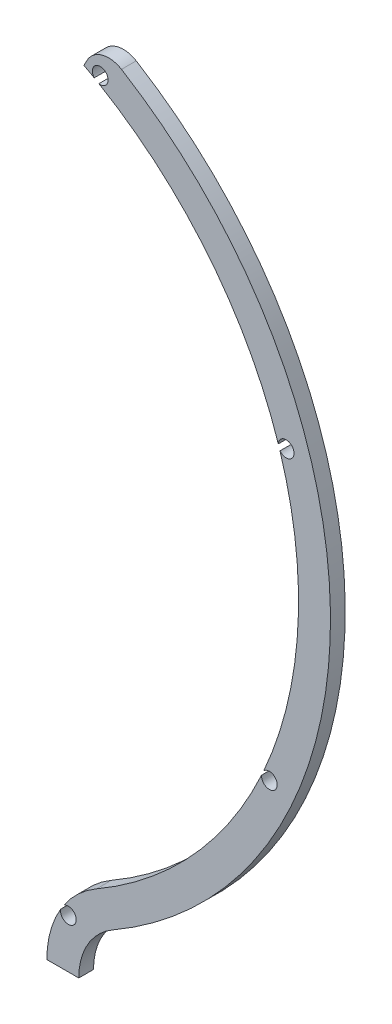
SolidWorks part; units mm, degrees
material "Thornel Mat VMA"
ref_plane "Front Plane" through (0, 0, 0) normal (0, 0, 1) x (1, 0, 0)
ref_plane "Top Plane" through (0, 0, 0) normal (0, 1, 0) x (1, 0, 0)
ref_plane "Right Plane" through (0, 0, 0) normal (1, 0, 0) x (0, 0, -1)
sketch "Sketch1" plane through (0, 0, 0) normal (0, 0, 1) x (1, 0, 0)
  line L0 (23.5, 0) -> (35.5, 0) construction
  line L1 (31, 0) -> (37.5, 0)
  line L3 (39.1768, 162.602) -> (38.5438, 161.4089)
  circle A0 centre (41.8718, 161.2805) radius 1.6
  circle A1 centre (79.7216, 114.3972) radius 1.6
  circle A2 centre (76.2992, 54.2395) radius 1.6
  circle A3 centre (35.3905, 10) radius 1.6
  arc A4 (38.5438, 161.4089) -> (41.1218, 17.5314) centre (0, 88.7564) cw
  arc A5 (41.1218, 17.5314) -> (31, 0) centre (51.2436, 0) ccw
  arc A6 (43.3718, 13.6343) -> (35.5, 0) centre (51.2436, 0) ccw construction
  arc A7 (43.3718, 13.6343) -> (15.0629, 174.1822) centre (0, 88.7564) ccw construction
  arc A8 (46.1965, 164.5278) -> (44.3718, 11.9023) centre (0, 88.7564) cw
  arc A9 (44.3718, 11.9023) -> (37.5, 0) centre (51.2436, 0) ccw
  arc A10 (46.1965, 164.5278) -> (39.1768, 162.602) centre (43.5937, 160.2587) ccw
  point P30 (0, 0)
  point P31 (0, 88.7564)
  dimension "D1" = 3.2
  dimension "D2" = 4.5
  dimension "D3" = 2
  dimension "D5" = 5
  dimension "D4" = 3
extrude "Boss-Extrude1" add sketch "Sketch1" along normal blind 3 contours A8 A10 L3 A4 A0 A1 A2 A5 A3 L1 A9 region at (33.4062, 4.8807, 0)
